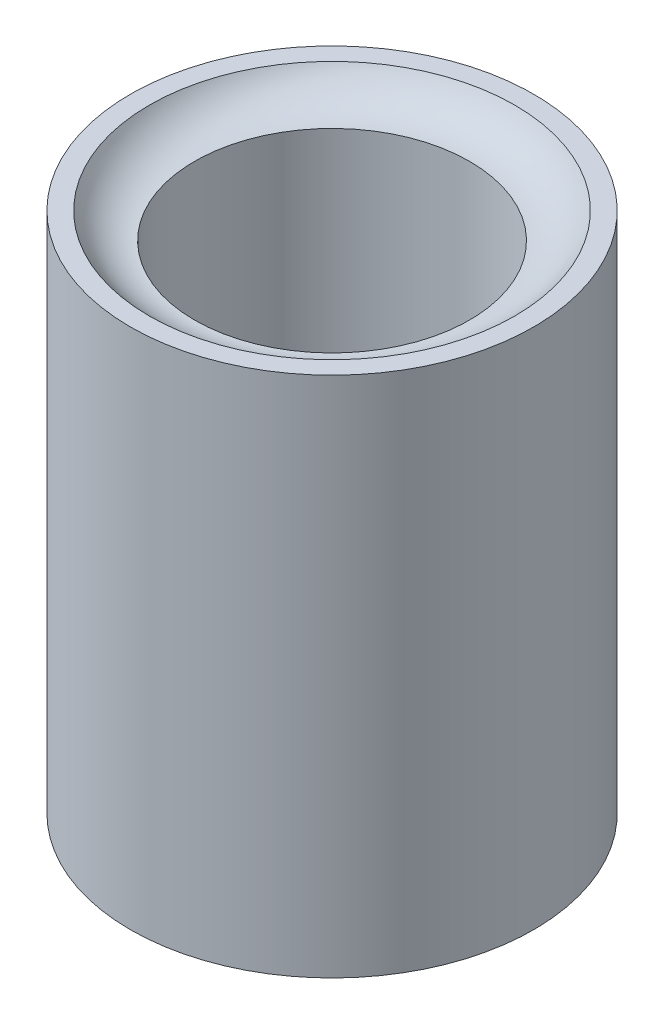
SolidWorks part; units mm, degrees
ref_plane "前基準面" through (0, 0, 0) normal (0, 0, 1) x (1, 0, 0)
ref_plane "上基準面" through (0, 0, 0) normal (0, 1, 0) x (1, 0, 0)
ref_plane "右基準面" through (0, 0, 0) normal (1, 0, 0) x (0, 0, -1)
sketch "草圖1" plane through (0, 0, 0) normal (0, 1, 0) x (1, 0, 0)
  circle A0 centre (0, 0) radius 38.625
  dimension "D1" = 77.25
extrude "填料-伸長1" add sketch "草圖1" along normal blind 100
sketch "草圖2" plane through (0, 100, 0) normal (0, 1, 0) x (1, 0, 0)
  circle A0 centre (0, 0) radius 35
  dimension "D1" = 70
extrude "除料-伸長3" cut sketch "草圖2" against normal blind 5 contours A0
sketch "草圖3" plane through (0, 100, 0) normal (0, 1, 0) x (1, 0, 0)
fillet "圓角8" radius 10 1 edges at (0, 95, 35)
sketch "草圖4" plane through (0, 95, 0) normal (0, 1, 0) x (1, 0, 0)
  circle A0 centre (0, 0) radius 26.3397
extrude "除料-伸長4" cut sketch "草圖4" against normal blind 97.6654
